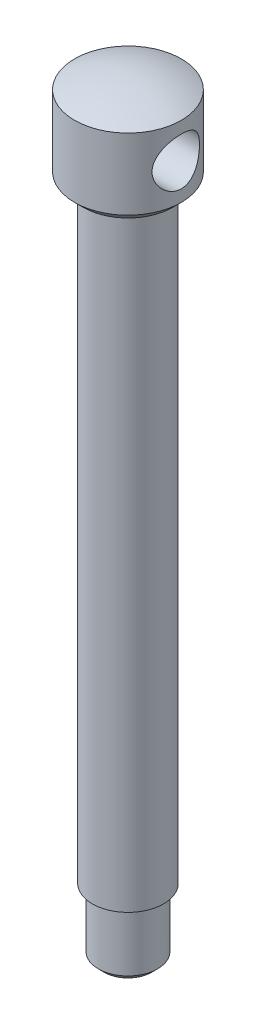
SolidWorks part; units mm, degrees
ref_plane "Front Plane" through (0, 0, 0) normal (0, 0, 1) x (1, 0, 0)
ref_plane "Top Plane" through (0, 0, 0) normal (0, 1, 0) x (1, 0, 0)
ref_plane "Right Plane" through (0, 0, 0) normal (1, 0, 0) x (0, 0, -1)
sketch "Sketch1" plane through (0, 0, 0) normal (0, 1, 0) x (1, 0, 0)
  circle A0 centre (0, 0) radius 18
  dimension "D1" = 36
extrude "Boss-Extrude1" add sketch "Sketch1" along normal blind 24
sketch "Sketch2" plane through (0, 0, 0) normal (1, 0, 0) x (0, 0, -1)
  circle A0 centre (0, 12) radius 8
  dimension "D1" = 16
  dimension "D2" = 12
extrude "Cut-Extrude1" cut sketch "Sketch2" against normal blind 24 and the other way blind 24
dome "Dome1" faces to dome 1 distance 4 reverse direction no elliptical dome no face at (0, 24, 18) parameters "D1"=4
sketch "Sketch3" plane through (0, 0, 0) normal (1, 0, 0) x (0, 0, -1)
  line L0 (0, 0) -> (0, -2.8284)
  line L1 (0, 0) -> (18, 0)
  line L2 (18, 0) -> (15.1716, -2.8284)
  line L3 (15.1716, -2.8284) -> (0, -2.8284)
  dimension "D1" = 45
  dimension "D2" = 18
  dimension "D3" = 4
revolve "Revolve1" add sketch "Sketch3" angle 360 about L0
sketch "Sketch5" plane through (0, 0, 0) normal (0, 1, 0) x (1, 0, 0)
  circle A0 centre (0, 0) radius 12
  dimension "D1" = 24
extrude "Boss-Extrude3" add sketch "Sketch5" against normal blind 208
cosmetic thread "Cosmetic Thread1" parameters "D2"=20.704
sketch "Sketch13" plane through (0, -208, 0) normal (0, -1, 0) x (-1, 0, 0)
  circle A0 centre (0, 0) radius 10
  dimension "D1" = 20
extrude "Boss-Extrude4" add sketch "Sketch13" along normal blind 20
sketch "Sketch14" plane through (0, 0, 0) normal (1, 0, 0) x (0, 0, -1)
  line L0 (0, -228) -> (0, -230)
  line L1 (-10, -228) -> (10, -228) construction
  line L2 (0, -230) -> (-8, -230)
  line L3 (-8, -230) -> (-10, -228)
  line L4 (-10, -228) -> (0, -228)
  dimension "D1" = 2
  dimension "D2" = 45
revolve "Revolve2" add sketch "Sketch14" angle 360 about L0
hole_wizard "M8 Tapped Hole1" positions "Sketch16" profile "Sketch18" tap size "M8" standard "ISO"
sketch "Sketch16" plane through (0, -230, 0) normal (0, -1, 0) x (-1, 0, 0)
  point P0 (0, 0)
sketch "Sketch18" plane through (0, -230, 0) normal (1, 0, 0) x (0, 0, -1)
  line L0 (0, 0) -> (0, 22.0429)
  line L1 (0, 22.0429) -> (3.4, 20)
  line L2 (3.4, 20) -> (3.4, 0)
  line L5 (3.4, 0) -> (0, 0)
  line L10 (0, 22.0429) -> (-3.4, 20) construction
  line L11 (0, -6.35) -> (0, 107.95) construction
  dimension "Tap Drill Dia." = 6.8
  dimension "Tap Drill Depth" = 20
  dimension "Drill Angle" = 118
cosmetic thread "Hole Thread1" parameters "D1"=20, "D2"=8
